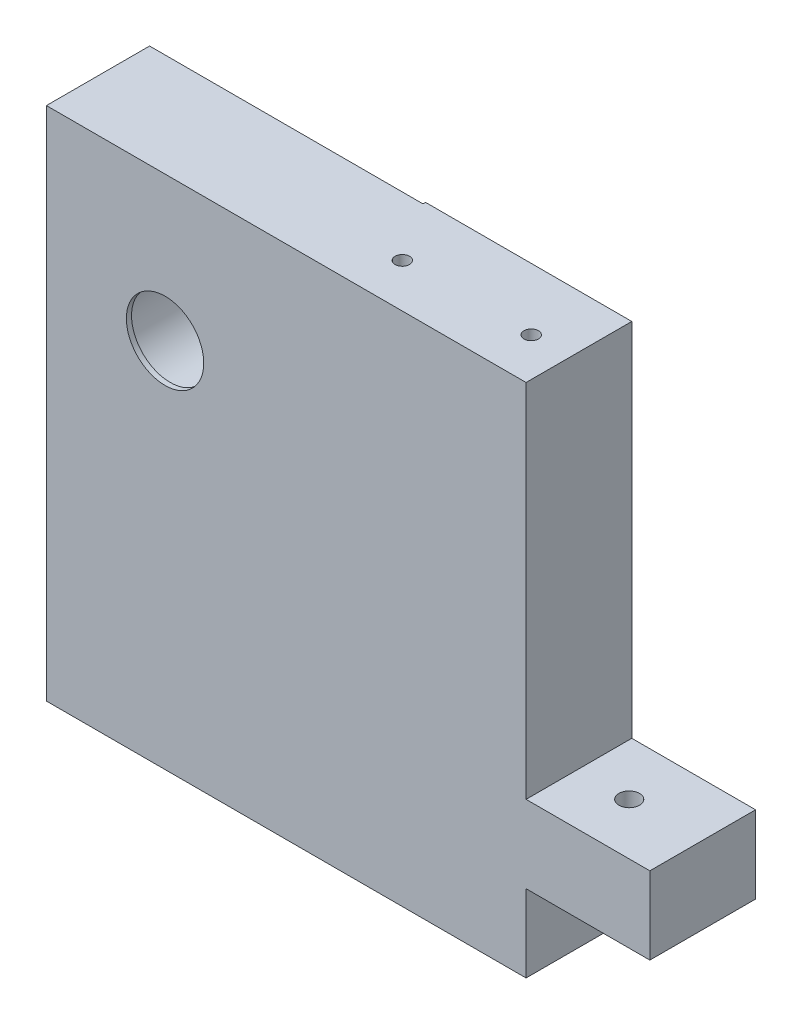
SolidWorks part; units mm, degrees
ref_plane "Front Plane" through (0, 0, 0) normal (0, 0, 1) x (1, 0, 0)
ref_plane "Top Plane" through (0, 0, 0) normal (0, 1, 0) x (1, 0, 0)
ref_plane "Right Plane" through (0, 0, 0) normal (1, 0, 0) x (0, 0, -1)
sketch "Sketch1" plane through (0, 0, 0) normal (0, 0, 1) x (1, 0, 0)
  line L1 (-76.1871, 64.9281) -> (16.8129, 64.9281)
  line L2 (-76.1871, 64.9281) -> (-76.1871, -35.0719)
  line L3 (-76.1871, -35.0719) -> (16.8129, -35.0719)
  line L4 (16.8129, 64.9281) -> (16.8129, -35.0719)
  dimension "D1" = 93
  dimension "D2" = 100
extrude "Boss-Extrude2" add sketch "Sketch1" along normal blind 20 contours L1 L4 L3 L2
sketch "Sketch3" plane through (0, 0, 0) normal (0, 0, -1) x (-1, 0, 0)
  line L0 (76.1871, -35.0719) -> (-16.8129, -35.0719) construction
  line L1 (-16.8129, 64.9281) -> (23.1871, 64.9281)
  line L2 (-16.8129, 64.9281) -> (-16.8129, -35.0719)
  line L3 (-16.8129, -35.0719) -> (23.1871, -35.0719)
  line L4 (23.1871, 64.9281) -> (23.1871, -35.0719)
  line L5 (-16.8129, 64.9281) -> (-16.8129, -35.0719) construction
  dimension "D1" = 0
  dimension "D2" = 0
  dimension "D3" = 40
  dimension "D4" = 100
extrude "Boss-Extrude3" add sketch "Sketch3" along normal blind 0.5
sketch "Sketch4" plane through (16.8129, 0, 0) normal (1, 0, 0) x (0, 0, -1)
  line L0 (-20, 64.9281) -> (-20, -35.0719) construction
  line L1 (-20, -5.0719) -> (0.5, -5.0719)
  line L2 (-20, -5.0719) -> (-20, -20.0719)
  line L3 (-20, -20.0719) -> (0.5, -20.0719)
  line L4 (0.5, -5.0719) -> (0.5, -20.0719)
  line L5 (0.5, 64.9281) -> (0.5, -35.0719) construction
  line L6 (-20, -35.0719) -> (0.5, -35.0719) construction
  dimension "D1" = 15
  dimension "D2" = 15
extrude "Boss-Extrude4" add sketch "Sketch4" along normal blind 24
sketch "Sketch5" plane through (0, -5.0719, 0) normal (0, 1, 0) x (1, 0, 0)
  line L0 (40.8129, -20) -> (16.8129, -20) construction
  line L2 (16.8129, 0.5) -> (16.8129, -20) construction
  circle A0 centre (26.8129, -10) radius 2
  dimension "D2" = 4
  dimension "D3" = 10
  dimension "D1" = 10
extrude "Cut-Extrude1" cut sketch "Sketch5" against normal blind 50
sketch "Sketch6" plane through (0, 0, -0.5) normal (0, 0, -1) x (-1, 0, 0)
  line L0 (-16.8129, -35.0719) -> (23.1871, -35.0719) construction
  line L1 (-16.8129, -20.0719) -> (-16.8129, -35.0719) construction
  circle A0 centre (-1.8129, -24.5719) radius 7.5
  dimension "D1" = 15
  dimension "D2" = 10.5
  dimension "D3" = 15
sketch "Sketch7" plane through (0, 0, 0) normal (0, 0, -1) x (-1, 0, 0)
  line L0 (76.1871, -35.0719) -> (23.1871, -35.0719) construction
  line L2 (-16.8129, 64.9281) -> (-16.8129, -5.0719) construction
  circle A0 centre (53.1871, 36.9281) radius 9.5
  dimension "D1" = 19
  dimension "D2" = 72
  dimension "D3" = 70
extrude "Cut-Extrude3" cut sketch "Sketch7" against normal blind 50
extrude "Extrude-Thin1" add sketch "Sketch7<2>" along normal blind 1 from surface thin starting at face at (-43.6871, 36.9281, 20) thin type one direction reverse wall 2
sketch "Sketch7<2>" plane through (0, 0, 0) normal (0, 0, -1) x (-1, 0, 0) same geometry as "Sketch7"
extrude "Extrude-Thin2" add sketch "Sketch6" along normal blind 1 from surface thin starting at face at (-0.4371, 1.1781, 20) thin type one direction reverse wall 2
sketch "Sketch8" plane through (0, 64.9281, 0) normal (0, 1, 0) x (1, 0, 0)
  line L0 (-76.1871, -20) -> (16.8129, -20) construction
  line L1 (16.8129, 0.5) -> (-23.1871, 0.5)
  line L2 (16.8129, 0.5) -> (16.8129, -20)
  line L3 (16.8129, -20) -> (-23.1871, -20)
  line L4 (-23.1871, 0.5) -> (-23.1871, -20)
  line L5 (16.8129, 0.5) -> (-23.1871, -20) construction
  line L6 (16.8129, -20) -> (-23.1871, 0.5) construction
  line L7 (-23.1871, 0.5) -> (-23.1871, 0) construction
  circle A0 centre (9.3129, -11.5) radius 1.4
  circle A1 centre (-15.6871, -11.5) radius 1.4
  point P4 (-3.1871, -9.75)
  dimension "D1" = 25
  dimension "D2" = 7.5
  dimension "D3" = 2.8
  dimension "D4" = 2.8
  dimension "D5" = 12
  dimension "D6" = 12
extrude "Cut-Extrude4" cut sketch "Sketch8" against normal blind 20 contours A1 | A0 region at (-15.6871, 64.9281, 11.5)
sketch "Sketch11" plane through (0, 0, -0.5) normal (0, 0, -1) x (-1, 0, 0)
  line L1 (20.64, 55.6781) -> (-16.1019, 55.6781)
  line L2 (20.64, 55.6781) -> (20.64, 18.1781)
  line L3 (20.64, 18.1781) -> (-16.1019, 18.1781)
  line L4 (-16.1019, 55.6781) -> (-16.1019, 18.1781)
  circle A0 centre (53.1871, 36.9281) radius 9.5 construction
  dimension "D1" = 18.75
  dimension "D2" = 37.5
extrude "Cut-Extrude6" cut sketch "Sketch11" against normal blind 8.5
